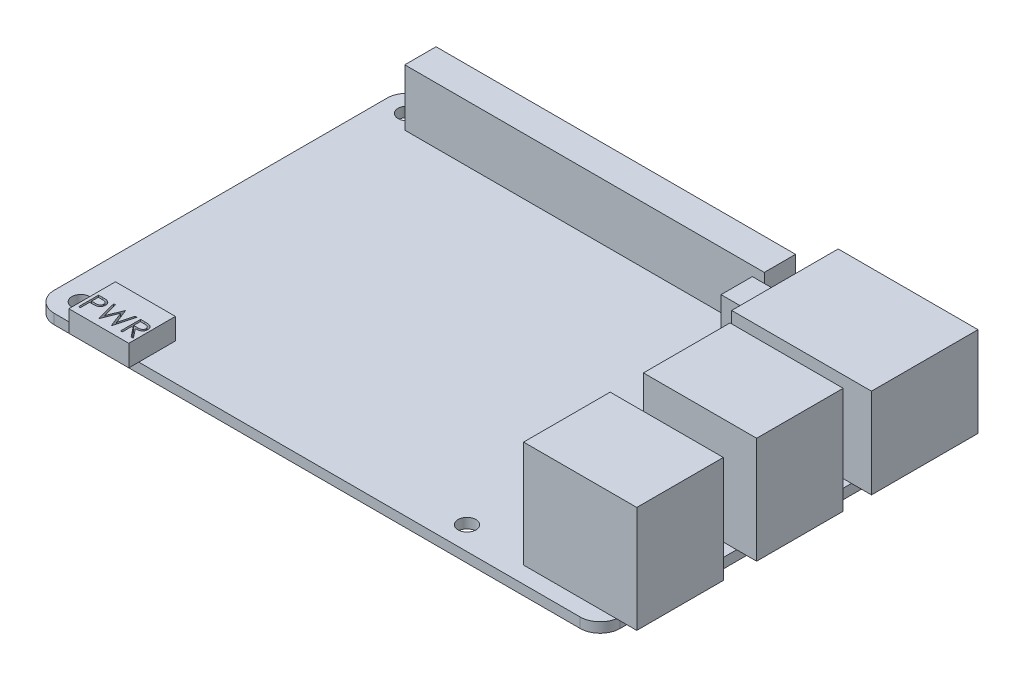
SolidWorks part; units mm, degrees
ref_plane "Front Plane" through (0, 0, 0) normal (0, 0, 1) x (1, 0, 0)
ref_plane "Top Plane" through (0, 0, 0) normal (0, 1, 0) x (1, 0, 0)
ref_plane "Right Plane" through (0, 0, 0) normal (1, 0, 0) x (0, 0, -1)
sketch "Sketch1" plane through (0, 0, 0) normal (0, 1, 0) x (1, 0, 0)
  line L0 (3.5, 52.5) -> (61.5, 52.5) construction
  line L1 (0, 0) -> (85, 0)
  line L2 (0, 0) -> (0, 56)
  line L3 (0, 56) -> (85, 56)
  line L4 (85, 0) -> (85, 56)
  line L5 (61.5, 52.5) -> (61.5, 3.5) construction
  line L6 (61.5, 3.5) -> (3.5, 3.5) construction
  line L7 (3.5, 3.5) -> (3.5, 52.5) construction
  circle A0 centre (3.5, 52.5) radius 1.35
  circle A1 centre (3.5, 3.5) radius 1.35
  circle A2 centre (61.5, 3.5) radius 1.35
  circle A3 centre (61.5, 52.5) radius 1.35
  dimension "D5" = 2.7
  dimension "D6" = 3.5
  dimension "D7" = 3.5
  dimension "D1" = 85
  dimension "D2" = 56
  dimension "D3" = 58
  dimension "D4" = 49
extrude "Boss-Extrude1" add sketch "Sketch1" along normal blind 1.5
fillet "Fillet1" radius 3 4 edges at (85, 0.75, -56) (85, 0.75, 0) (0, 0.75, -56) (0, 0.75, 0)
sketch "Sketch2" plane through (0, 1.5, 0) normal (0, 1, 0) x (1, 0, 0)
  line L0 (3, 0) -> (82, 0) construction
  line L1 (88, 20.5) -> (71, 20.5)
  line L2 (88, 20.5) -> (88, 33.5)
  line L3 (88, 33.5) -> (71, 33.5)
  line L4 (71, 20.5) -> (71, 33.5)
  line L5 (88, 2.5) -> (71, 2.5)
  line L6 (88, 2.5) -> (88, 15.5)
  line L7 (88, 15.5) -> (71, 15.5)
  line L8 (71, 2.5) -> (71, 15.5)
  line L9 (85, 3) -> (85, 53) construction
  point P8 (88, 9)
  point P11 (88, 27)
  dimension "D1" = 17
  dimension "D2" = 13
  dimension "D3" = 9
  dimension "D4" = 27
  dimension "D5" = 3
extrude "Boss-Extrude2" add sketch "Sketch2" along normal blind 16
sketch "Sketch3" plane through (0, 1.5, 0) normal (0, 1, 0) x (1, 0, 0)
  line L0 (88, 20.5) -> (88, 33.5) construction
  line L1 (88, 37.75) -> (67, 37.75)
  line L2 (88, 37.75) -> (88, 53.75)
  line L3 (88, 53.75) -> (67, 53.75)
  line L4 (67, 37.75) -> (67, 53.75)
  line L5 (3, 0) -> (82, 0) construction
  point P6 (88, 45.75)
  dimension "D1" = 21
  dimension "D2" = 16
  dimension "D3" = 45.75
extrude "Boss-Extrude3" add sketch "Sketch3" along normal blind 13.5
sketch "Sketch4" plane through (0, 1.5, 0) normal (0, 1, 0) x (1, 0, 0)
  line L0 (61.5, 52.5) -> (61.5, 48.71) construction
  line L1 (5.5, 54.85) -> (59.5, 54.85)
  line L2 (5.5, 54.85) -> (5.5, 50.15)
  line L3 (5.5, 50.15) -> (59.5, 50.15)
  line L4 (59.5, 54.85) -> (59.5, 50.15)
  line L5 (59.15, 48.71) -> (63.85, 48.71)
  line L6 (59.15, 48.71) -> (59.15, 44.01)
  line L7 (59.15, 44.01) -> (63.85, 44.01)
  line L8 (63.85, 48.71) -> (63.85, 44.01)
  line L9 (3.5, 52.5) -> (61.5, 52.5) construction
  point P11 (63.85, 46.36)
  point P13 (32.5, 52.5)
  point P15 (32.5, 54.85)
  point P16 (5.5, 52.5)
  dimension "D1" = 6.14
  dimension "D2" = 54
  dimension "D3" = 4.7
  dimension "D4" = 4.7
extrude "Boss-Extrude4" add sketch "Sketch4" along normal blind 8.5
sketch "Sketch5" plane through (0, 1.5, 0) normal (0, 1, 0) x (1, 0, 0)
  line L0 (3, 0) -> (82, 0) construction
  line L1 (6.7, -1.5) -> (15.7, -1.5)
  line L2 (6.7, -1.5) -> (6.7, 5.5)
  line L3 (6.7, 5.5) -> (15.7, 5.5)
  line L4 (15.7, -1.5) -> (15.7, 5.5)
  circle A0 centre (3.5, 3.5) radius 1.35 construction
  point P8 (11.2, -1.5)
  dimension "D4" = 7.7
  dimension "D1" = 9
  dimension "D2" = 7
  dimension "D3" = 1.5
extrude "Boss-Extrude5" add sketch "Sketch5" along normal blind 3.2
sketch "Sketch6" plane through (0, 4.7, 0) normal (0, 1, 0) x (1, 0, 0)
  line L0 (6.7, -0.5) -> (15.7, -0.5) construction
  line L1 (6.7, 5.5) -> (6.7, -1.5) construction
  line L2 (15.7, -1.5) -> (15.7, 5.5) construction
  line L3 (6.7, -1.5) -> (15.7, -1.5) construction
  text T0 "PWR" font "Century Gothic" height 3
  dimension "D1" = 1
extrude "Cut-Extrude1" cut sketch "Sketch6" against normal blind 1
